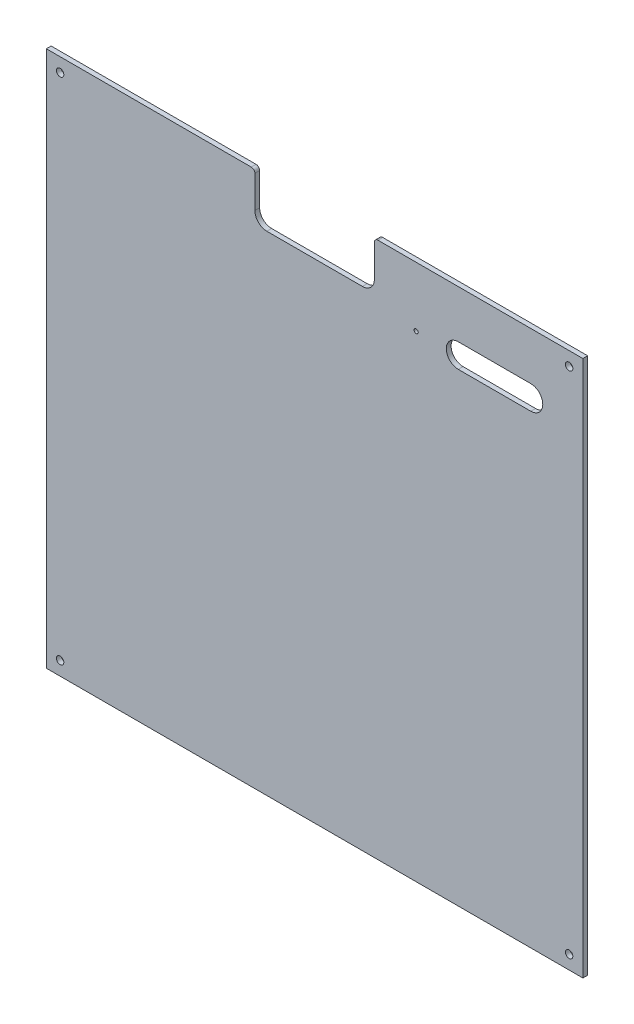
SolidWorks part; units mm, degrees
material "ABS PC"
ref_plane "Piano frontale" through (0, 0, 0) normal (0, 0, 1) x (1, 0, 0)
ref_plane "Piano superiore" through (0, 0, 0) normal (0, 1, 0) x (1, 0, 0)
ref_plane "Piano destro" through (0, 0, 0) normal (1, 0, 0) x (0, 0, -1)
sketch "Schizzo1" plane through (0, 0, 0) normal (0, 0, 1) x (1, 0, 0)
  line L0 (0, 0) -> (0, 449)
  line L1 (0, 449) -> (171.5, 449)
  line L2 (449, 449) -> (449, 0)
  line L3 (449, 0) -> (0, 0)
  line L4 (174.5, 446) -> (174.5, 419)
  line L5 (184.5, 409) -> (264.5, 409)
  line L6 (274.5, 419) -> (274.5, 446)
  line L7 (277.5, 449) -> (449, 449)
  line L8 (154.5, 399) -> (294.5, 399) construction
  line L9 (224.5, 379) -> (224.5, 419) construction
  line L10 (344.7159, 399) -> (405.4404, 399) construction
  line L11 (344.7159, 409) -> (405.4404, 409)
  line L12 (344.7159, 389) -> (405.4404, 389)
  line L13 (0, 224.5) -> (449, 224.5) construction
  line L23 (73.9219, 399) -> (73.9219, 449) construction
  line L24 (174.5, 432.5) -> (314.5, 432.5) construction
  arc A0 (174.5, 419) -> (184.5, 409) centre (184.5, 419) ccw
  arc A1 (274.5, 419) -> (264.5, 409) centre (264.5, 419) cw
  circle A2 centre (11.5, 11.5) radius 3.1
  circle A3 centre (437.5, 11.5) radius 3.1
  circle A4 centre (437.5, 437.5) radius 3.1
  circle A5 centre (11.5, 437.5) radius 3.1
  circle A6 centre (309.5, 399) radius 1.75
  arc A7 (277.5, 449) -> (274.5, 446) centre (277.5, 446) ccw
  arc A8 (344.7159, 409) -> (344.7159, 389) centre (344.7159, 399) ccw
  arc A9 (405.4404, 389) -> (405.4404, 409) centre (405.4404, 399) ccw
  arc A10 (174.5, 446) -> (171.5, 449) centre (171.5, 446) ccw
  point P11 (174.5, 409)
  point P14 (274.5, 409)
  point P33 (375.0781, 399)
  point P44 (174.5, 449)
  dimension "D5" = 10
  dimension "D6" = 11.5
  dimension "D7" = 11.5
  dimension "D8" = 6.2
  dimension "D9" = 3.5
  dimension "D10" = 35
  dimension "D12" = 3
  dimension "D1" = 449
  dimension "D2" = 449
  dimension "D3" = 100
  dimension "D4" = 40
  dimension "D11" = 20
  dimension "D21" = 50
extrude "Estrusione-Estrusione1" add sketch "Schizzo1" along normal blind 4
